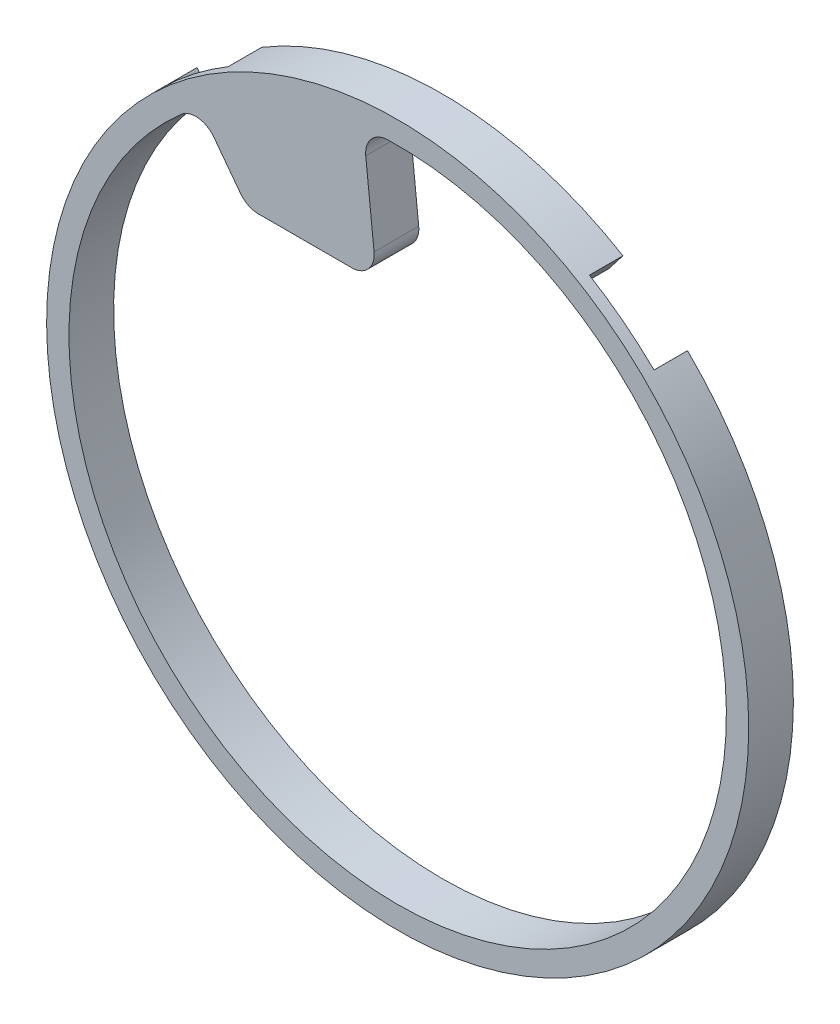
SolidWorks part; units mm, degrees
material "Acrylic (Medium-high impact)"
ref_plane "Front Plane" through (0, 0, 0) normal (0, 0, 1) x (1, 0, 0)
ref_plane "Top Plane" through (0, 0, 0) normal (0, 1, 0) x (1, 0, 0)
ref_plane "Right Plane" through (0, 0, 0) normal (1, 0, 0) x (0, 0, -1)
sketch "Sketch1" plane through (0, 0, 0) normal (0, 0, 1) x (1, 0, 0)
  circle A0 centre (0, 0) radius 24.9555
  circle A1 centre (0, 0) radius 24.9555 construction
  circle A2 centre (0, 0) radius 23.368
  dimension "D1" = 1.5875
extrude "Boss-Extrude1" add sketch "Sketch1" along normal blind 3.175
sketch "Sketch2" plane through (0, 0, 3.175) normal (0, 0, 1) x (1, 0, 0)
  line L0 (0, 0) -> (0, 23.368) construction
  line L1 (0, 0) -> (-2.4426, 23.24) construction
  line L2 (0, 0) -> (-14.0632, 18.6625) construction
  line L3 (-14.0632, 18.6625) -> (-10.7003, 14.1997)
  line L4 (-2.4426, 23.24) -> (-1.4925, 14.1997)
  line L5 (-10.7003, 14.1997) -> (-1.4925, 14.1997)
  circle A0 centre (0, 0) radius 23.368 construction
  circle A1 centre (0, 0) radius 17.78 construction
  arc A2 (-14.0632, 18.6625) -> (-2.4426, 23.24) centre (0, 0) cw
  dimension "D3" = 5.588
  dimension "D1" = 6
  dimension "D2" = 31
extrude "Boss-Extrude2" add sketch "Sketch2" against normal through all
fillet "Fillet1" radius 1.6002 4 edges at (-1.4925, 14.1997, 1.5875) (-10.7003, 14.1997, 1.5875) (-14.0632, 18.6625, 1.5875) (-2.4426, 23.24, 1.5875)
sketch "Sketch3" plane through (0, 0, 0) normal (0, 0, -1) x (-1, 0, 0)
  line L0 (0, 0) -> (18.5855, 24.1075) construction
  line L1 (18.5855, 24.1075) -> (-18.5855, 24.1075) construction
  line L2 (-18.5855, 24.1075) -> (0, 0) construction
  line L3 (18.5855, 24.1075) -> (9.5822, 12.4291) construction
  line L4 (20.8822, 22.3369) -> (11.8789, 10.6585)
  line L5 (16.2888, 25.8781) -> (7.2854, 14.1997)
  line L6 (9.9024, 14.1997) -> (3.2697, 14.1997) construction
  line L7 (-18.5855, 24.1075) -> (-9.5822, 12.4291) construction
  line L8 (-16.2888, 25.8781) -> (-7.2854, 14.1997)
  line L9 (-20.8822, 22.3369) -> (-11.8789, 10.6585)
  arc A0 (20.8822, 22.3369) -> (16.2888, 25.8781) centre (18.5855, 24.1075) ccw
  arc A1 (7.2854, 14.1997) -> (11.8789, 10.6585) centre (9.5822, 12.4291) ccw
  arc A2 (15.755, 24.7383) -> (17.7601, 26.8875) centre (18.5855, 24.1075) ccw construction
  arc A3 (-16.2888, 25.8781) -> (-20.8822, 22.3369) centre (-18.5855, 24.1075) ccw
  arc A4 (-11.8789, 10.6585) -> (-7.2854, 14.1997) centre (-9.5822, 12.4291) ccw
  point P4 (14.0838, 18.2683)
  point P15 (-14.0838, 18.2683)
extrude "Cut-Extrude1" cut sketch "Sketch3" against normal offset from surface (2.3812 mm away) 0.7937 up to face at (24.9555, 0, 3.175)
